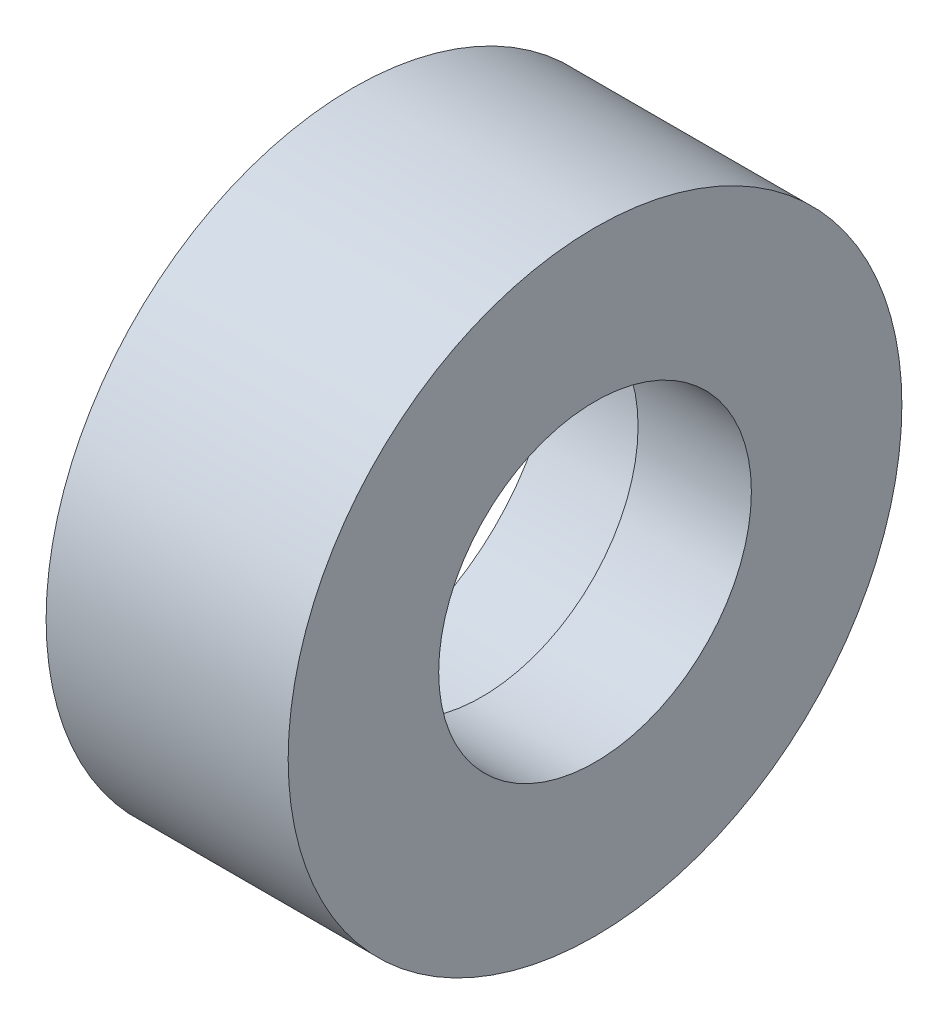
SolidWorks part; units mm, degrees
ref_plane "Ebene vorne" through (0, 0, 0) normal (0, 0, 1) x (1, 0, 0)
ref_plane "Ebene oben" through (0, 0, 0) normal (0, 1, 0) x (1, 0, 0)
ref_plane "Ebene rechts" through (0, 0, 0) normal (1, 0, 0) x (0, 0, -1)
sketch "Skizze4" plane through (0, 0, 0) normal (0, 0, 1) x (1, 0, 0)
  line L0 (0, 11) -> (7, 11)
  line L1 (0, 11) -> (0, 16.6831)
  line L2 (0, 16.6831) -> (13.1594, 16.6831)
  line L3 (13.1594, 16.6831) -> (13.1594, 8.5)
  line L4 (13.1594, 8.5) -> (7, 8.5)
  line L5 (7, 8.5) -> (7, 11)
  line L6 (0, 0) -> (13.1594, 0) construction
  dimension "D1" = 11
  dimension "D2" = 7
  dimension "D3" = 2.5
revolve "Rotation1" add sketch "Skizze4" angle 360 about L6
